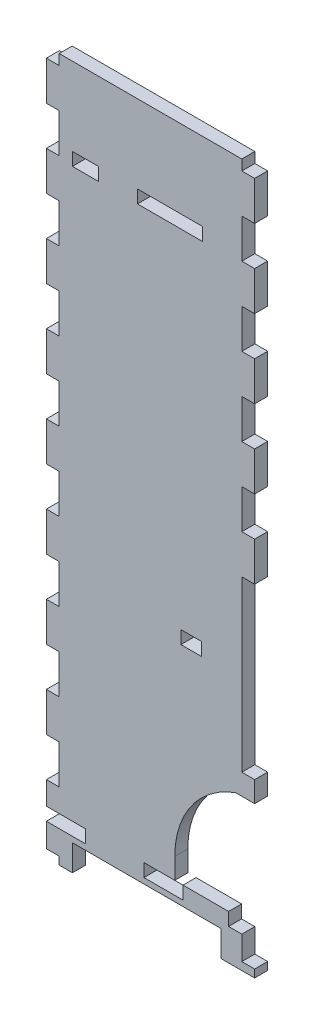
SolidWorks part; units mm, degrees
material "Balsa"
ref_plane "Plan de face" through (0, 0, 0) normal (0, 0, 1) x (1, 0, 0)
ref_plane "Plan de dessus" through (0, 0, 0) normal (0, 1, 0) x (1, 0, 0)
ref_plane "Plan de droite" through (0, 0, 0) normal (1, 0, 0) x (0, 0, -1)
sketch "Esquisse1" plane through (0, 0, 0) normal (0, 0, 1) x (1, 0, 0)
  line L0 (49.3309, 25.1093) -> (120.4109, 25.1093) construction
  line L1 (0, 0) -> (80, 0)
  line L2 (0, 0) -> (0, 270)
  line L3 (0, 270) -> (80, 270)
  line L4 (80, 59.7791) -> (80, 270)
  line L5 (49.3309, 25.1093) -> (49.3309, 17.15)
  line L6 (49.3309, 17.15) -> (80, 17.15)
  line L7 (80, 17.15) -> (80, 0)
  ellipse E0 centre (84.8709, 25.1093) end of major axis (120.4109, 25.1093) minor radius 35 (49.3309, 25.1093) -> (80, 59.7791) cw
  point P5 (84.8709, 25.1093)
  dimension "D1" = 80
  dimension "D2" = 270
  dimension "D3" = 80
  dimension "D4" = 70
  dimension "D5" = 71.08
extrude "Boss.-Extru.1" add sketch "Esquisse1" along normal blind 5
sketch "Esquisse2" plane through (0, 0, 5) normal (0, 0, 1) x (1, 0, 0)
  line L0 (80, 0) -> (80, 17.15) construction
  line L1 (51.6797, 101.7504) -> (59.6797, 101.7504)
  line L2 (51.6797, 101.7504) -> (51.6797, 96.7504)
  line L3 (51.6797, 96.7504) -> (59.6797, 96.7504)
  line L4 (59.6797, 101.7504) -> (59.6797, 96.7504)
  line L5 (75.08, 12.15) -> (70, 12.15)
  line L6 (80, 17.15) -> (80, 3)
  line L7 (80, 3) -> (75.08, 3)
  line L8 (75.08, 12.15) -> (75.08, 3)
  line L9 (80, 59.7791) -> (80, 270) construction
  line L10 (0, 0) -> (80, 0) construction
  line L11 (70, 12.15) -> (70, 17.15)
  line L12 (80, 17.15) -> (49.3309, 17.15) construction
  line L13 (70, 17.15) -> (80, 17.15)
  line L14 (0, 270) -> (0, 0) construction
  line L15 (37.5, 17.15) -> (52.5, 17.15)
  line L16 (37.5, 17.15) -> (37.5, 12.15)
  line L17 (37.5, 12.15) -> (52.5, 12.15)
  line L18 (52.5, 17.15) -> (52.5, 12.15)
  line L19 (15, 17.15) -> (0, 17.15)
  line L20 (15, 17.15) -> (15, 12.15)
  line L21 (15, 12.15) -> (0, 12.15)
  line L22 (0, 17.15) -> (0, 12.15)
  line L23 (80, 131) -> (75.08, 131)
  line L24 (0, 0) -> (4.92, 0)
  line L25 (0, 0) -> (0, 3)
  line L26 (0, 3) -> (4.92, 3)
  line L27 (4.92, 0) -> (4.92, 3)
  line L28 (80, 131) -> (80, 66)
  line L29 (80, 66) -> (75.08, 66)
  line L30 (75.08, 131) -> (75.08, 66)
  line L31 (0, 0) -> (80, 0) construction
  line L32 (80, 191) -> (75.08, 191)
  line L33 (80, 161) -> (75.08, 161)
  line L34 (80, 161) -> (80, 146)
  line L35 (80, 146) -> (75.08, 146)
  line L36 (75.08, 161) -> (75.08, 146)
  line L37 (80, 191) -> (80, 176)
  line L38 (80, 176) -> (75.08, 176)
  line L39 (75.08, 191) -> (75.08, 176)
  line L40 (80, 221) -> (75.08, 221)
  line L41 (80, 221) -> (80, 206)
  line L42 (80, 206) -> (75.08, 206)
  line L43 (75.08, 221) -> (75.08, 206)
  line L44 (80, 251) -> (75.08, 251)
  line L45 (80, 251) -> (80, 236)
  line L46 (80, 236) -> (75.08, 236)
  line L47 (75.08, 251) -> (75.08, 236)
  line L48 (80, 281) -> (75.08, 281)
  line L49 (80, 281) -> (80, 266)
  line L50 (80, 266) -> (75.08, 266)
  line L51 (75.08, 281) -> (75.08, 266)
  line L52 (0, 270) -> (0, 0) construction
  line L53 (0, 266) -> (4.92, 266)
  line L54 (0, 266) -> (0, 281)
  line L55 (0, 281) -> (4.92, 281)
  line L56 (4.92, 266) -> (4.92, 281)
  line L57 (80, 270) -> (0, 270) construction
  line L58 (0, 236) -> (4.92, 236)
  line L59 (0, 236) -> (0, 251)
  line L60 (0, 251) -> (4.92, 251)
  line L61 (4.92, 236) -> (4.92, 251)
  line L62 (0, 206) -> (4.92, 206)
  line L63 (0, 206) -> (0, 221)
  line L64 (0, 221) -> (4.92, 221)
  line L65 (4.92, 206) -> (4.92, 221)
  line L66 (0, 176) -> (4.92, 176)
  line L67 (0, 176) -> (0, 191)
  line L68 (0, 191) -> (4.92, 191)
  line L69 (4.92, 176) -> (4.92, 191)
  line L70 (0, 146) -> (4.92, 146)
  line L71 (0, 146) -> (0, 161)
  line L72 (0, 161) -> (4.92, 161)
  line L73 (4.92, 146) -> (4.92, 161)
  line L74 (0, 116) -> (4.92, 116)
  line L75 (0, 116) -> (0, 131)
  line L76 (0, 131) -> (4.92, 131)
  line L77 (4.92, 116) -> (4.92, 131)
  line L78 (0, 86) -> (4.92, 86)
  line L79 (0, 86) -> (0, 101)
  line L80 (0, 101) -> (4.92, 101)
  line L81 (4.92, 86) -> (4.92, 101)
  line L82 (0, 56) -> (4.92, 56)
  line L83 (0, 56) -> (0, 71)
  line L84 (0, 71) -> (4.92, 71)
  line L85 (4.92, 56) -> (4.92, 71)
  line L86 (0, 26) -> (4.92, 26)
  line L87 (0, 26) -> (0, 41)
  line L88 (0, 41) -> (4.92, 41)
  line L89 (4.92, 26) -> (4.92, 41)
  line L91 (10, 235) -> (20, 235)
  line L92 (10, 235) -> (10, 240)
  line L93 (10, 240) -> (20, 240)
  line L94 (20, 235) -> (20, 240)
  line L95 (80, 270) -> (0, 270) construction
  line L96 (35, 235) -> (60, 235)
  line L97 (35, 235) -> (35, 240)
  line L98 (35, 240) -> (60, 240)
  line L99 (60, 235) -> (60, 240)
  dimension "D1" = 4.92
  dimension "D2" = 3
  dimension "D3" = 10
  dimension "D4" = 5
  dimension "D5" = 5
  dimension "D6" = 15
  dimension "D7" = 27.5
  dimension "D8" = 5
  dimension "D9" = 15
  dimension "D10" = 4.92
  dimension "D11" = 3
  dimension "D12" = 4.92
  dimension "D13" = 66
  dimension "D14" = 65
  dimension "D15" = 15
  dimension "D16" = 15
  dimension "D18" = 15
  dimension "D19" = 4
  dimension "D21" = 5
  dimension "D22" = 30
  dimension "D17" = 5
  dimension "D20" = 9
extrude "Enlèv. mat.-Extru.1" cut sketch "Esquisse2" against normal blind 5
sketch "Esquisse3" plane through (0, 0, 0) normal (0, 0, -1) x (-1, 0, 0)
  line L0 (-80, 59.7791) -> (-80, 66) construction
  line L1 (-80, 61.9473) -> (-72.7194, 61.9473)
  line L2 (-80, 61.9473) -> (-80, 58)
  line L3 (-80, 58) -> (-72.7194, 58)
  line L4 (-72.7194, 61.9473) -> (-72.7194, 58)
  line L5 (-4.92, 0) -> (-80, 0) construction
  ellipse E0 centre (-84.8709, 25.1093) end of major axis (-120.4109, 25.1093) minor radius 35 (-49.3309, 25.1093) -> (-80, 59.7791) ccw construction
  dimension "D1" = 58
extrude "Boss.-Extru.2" add sketch "Esquisse3" against normal blind 5
sketch "Esquisse4" plane through (0, 0, 5) normal (0, 0, 1) x (1, 0, 0)
  line L0 (4.92, 0) -> (80, 0) construction
  line L1 (10, 0) -> (67, 0)
  line L2 (10, 0) -> (10, 10)
  line L3 (10, 10) -> (67, 10)
  line L4 (67, 0) -> (67, 10)
  line L5 (0, 12.15) -> (0, 3) construction
  line L6 (80, 0) -> (80, 3) construction
  dimension "D1" = 10
  dimension "D2" = 10
  dimension "D3" = 13
extrude "Enlèv. mat.-Extru.2" cut sketch "Esquisse4" against normal blind 5
